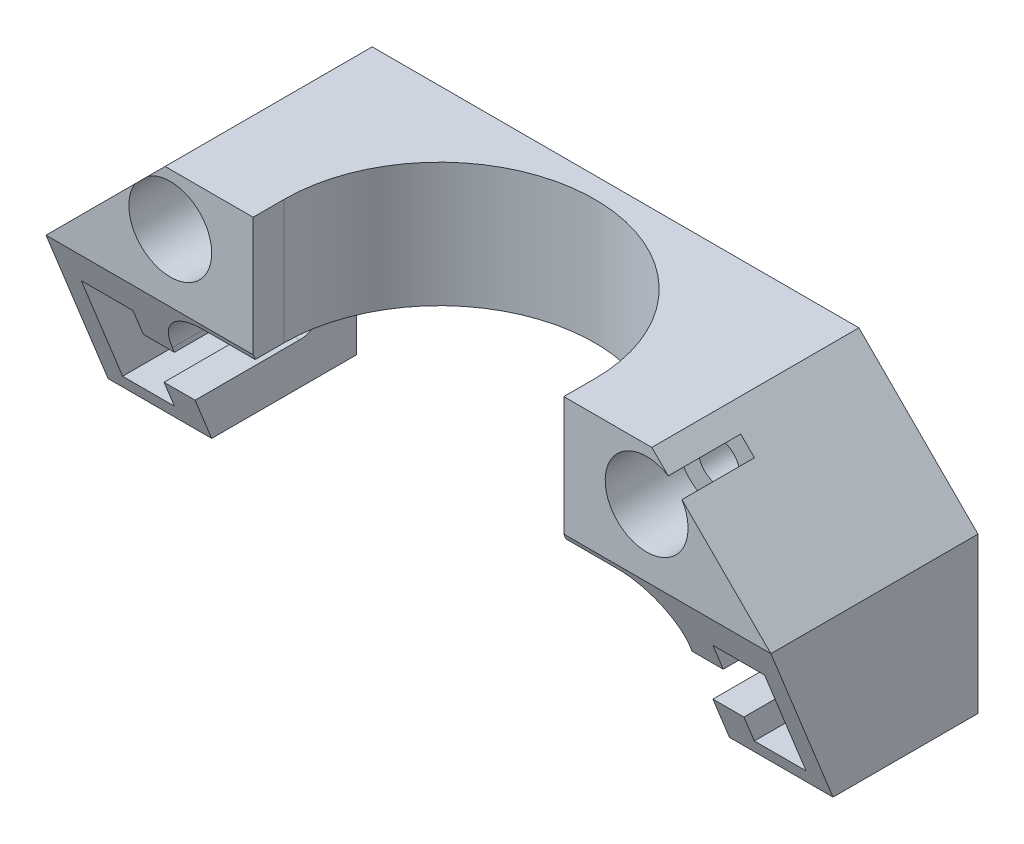
SolidWorks part; units mm, degrees
ref_plane "Front Plane" through (0, 0, 0) normal (0, 0, 1) x (1, 0, 0)
ref_plane "Top Plane" through (0, 0, 0) normal (0, 1, 0) x (1, 0, 0)
ref_plane "Right Plane" through (0, 0, 0) normal (1, 0, 0) x (0, 0, -1)
sketch "Sketch1" plane through (0, 0, 0) normal (0, 0, 1) x (1, 0, 0)
  line L0 (-23, 0) -> (23, 0) construction
  line L1 (-23.5, 5) -> (23.5, 5)
  line L2 (23.5, 5) -> (35, -6.5)
  line L3 (35, -6.5) -> (35, -21.5)
  line L4 (35, -21.5) -> (25, -21.5)
  line L5 (25, -21.5) -> (25, -12)
  line L6 (20, -7) -> (-20, -7)
  line L7 (-25, -12) -> (-25, -21.5)
  line L8 (-25, -21.5) -> (-35, -21.5)
  line L9 (-35, -21.5) -> (-35, -6.5)
  line L10 (-35, -6.5) -> (-23.5, 5)
  line L11 (0, 5) -> (0, 0) construction
  line L12 (0, 0) -> (0, -7) construction
  line L13 (-25, -21.5) -> (25, -21.5) construction
  line L14 (35, -6.5) -> (-35, -6.5) construction
  circle A0 centre (-23, 0) radius 2
  circle A1 centre (23, 0) radius 2
  arc A2 (25, -12) -> (20, -7) centre (20, -12) ccw
  arc A3 (-20, -7) -> (-25, -12) centre (-20, -12) ccw
  point P17 (0, -6.5)
  point P21 (25, -7)
  point P24 (-25, -7)
  dimension "D2" = 4
  dimension "D10" = 5
  dimension "D1" = 46
  dimension "D3" = 47
  dimension "D4" = 45
  dimension "D5" = 70
  dimension "D6" = 50
  dimension "D7" = 5
  dimension "D8" = 7
  dimension "D9" = 15
extrude "Boss-Extrude1" add sketch "Sketch1" along normal blind 20
sketch "Sketch2" plane through (0, 0, 20) normal (0, 0, 1) x (1, 0, 0)
  line L0 (-25, -21.5) -> (-25, -12) construction
  line L1 (-19.5, -12.5) -> (-30.5, -12.5)
  line L2 (-19.5, -12.5) -> (-19.5, -17.5)
  line L3 (-19.5, -17.5) -> (-30.5, -17.5)
  line L4 (-30.5, -12.5) -> (-30.5, -17.5)
  line L5 (-19.5, -12.5) -> (-30.5, -17.5) construction
  line L6 (-19.5, -17.5) -> (-30.5, -12.5) construction
  line L8 (-28, -20) -> (-33, -20)
  line L9 (-28, -20) -> (-28, -10)
  line L10 (-28, -10) -> (-33, -10)
  line L11 (-33, -20) -> (-33, -10)
  line L12 (-28, -20) -> (-33, -10) construction
  line L13 (-28, -10) -> (-33, -20) construction
  line L14 (-35, -21.5) -> (-25, -21.5) construction
  point P0 (-25, -16.75)
  point P7 (-30.5, -15)
  point P12 (-25, -16.75)
  point P15 (-23.0782, -17.5)
  point P16 (-25, -15)
  line M15 (-25, -21.5) -> (-25, -12)
  dimension "D1" = 5
  dimension "D2" = 5
  dimension "D3" = 3
  dimension "D4" = 10
  dimension "D5" = 1.5
extrude "Cut-Extrude1" cut sketch "Sketch2" against normal blind 17 contours L3 L2 L1 M15 | L9 L3 L1 M15 | L3 L9 L1 L4 | L11 L8 L9 L3 L4 L1 L10 region at (-22.25, -15, 20) region at (-26.5, -15, 20) region at (-29.25, -15, 20) region at (-30.9167, -15, 20)
fillet "Fillet1" radius 2.5 2 edges at (-26.5, -17.5, 3) (-26.5, -12.5, 3)
mirror "Mirror1" about plane through (0, 0, 0) normal (1, 0, 0) of "Fillet1", "Cut-Extrude1"
sketch "Sketch3" plane through (0, -7, 0) normal (0, -1, 0) x (1, 0, 0)
  line L0 (0, 17) -> (0, 0) construction
  line L1 (-20, 0) -> (20, 0) construction
  line L3 (-15, 47) -> (15, 47)
  line L4 (-15, 47) -> (-15, 17)
  line L6 (15, 47) -> (15, 17)
  line L7 (-15, 47) -> (15, 17) construction
  line L8 (-15, 17) -> (15, 47) construction
  arc A0 (-15, 17) -> (15, 17) centre (0, 17) ccw
  point P6 (0, 32)
  dimension "D1" = 30
  dimension "D2" = 17
extrude "Cut-Extrude2" cut sketch "Sketch3" against normal through all
sketch "Sketch4" plane through (0, 0, 0) normal (1, 0, 0) x (0, 0, -1)
  line L0 (-14, -21.5) -> (-20, -6.5)
  line L1 (-20, -21.5) -> (0, -21.5) construction
  line L2 (-20, -6.5) -> (-20, -21.5)
  line L3 (-20, -21.5) -> (-14, -21.5)
  line L4 (-20, -21.5) -> (-20, -6.5) construction
  point P5 (-20, -21.3653)
  point P9 (-20, -21.5)
  dimension "D1" = 6
extrude "Cut-Extrude3" cut sketch "Sketch4" against normal through all both and the other way through all
sketch "Sketch5" plane through (0, 0, 20) normal (0, 0, 1) x (1, 0, 0)
  circle A2 centre (-23, 0) radius 4
  circle A3 centre (-23, 0) radius 4
  circle A5 centre (23, 0) radius 4
  circle A6 centre (23, 0) radius 4
  dimension "D1" = 2
  dimension "D2" = 2
extrude "Cut-Extrude4" cut sketch "Sketch5" against normal blind 7
